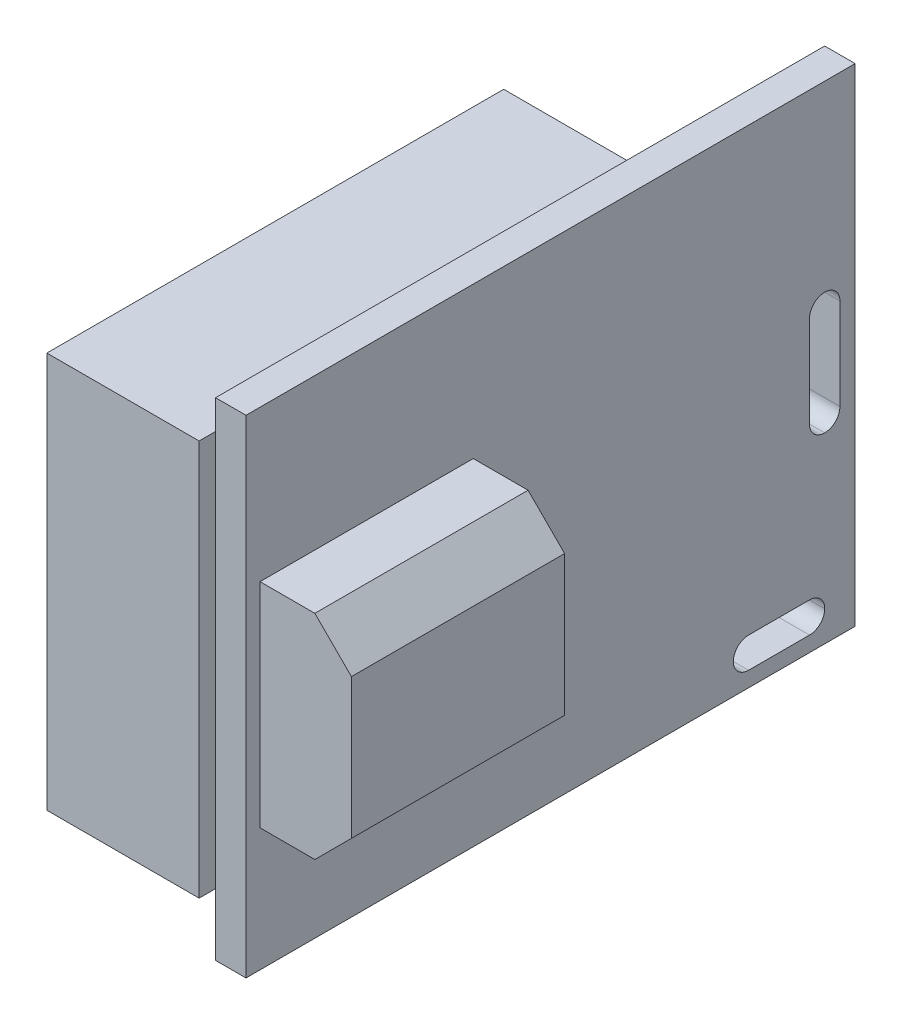
SolidWorks part; units mm, degrees
ref_plane "Спереди" through (0, 0, 0) normal (0, 0, 1) x (1, 0, 0)
ref_plane "Сверху" through (0, 0, 0) normal (0, 1, 0) x (1, 0, 0)
ref_plane "Справа" through (0, 0, 0) normal (1, 0, 0) x (0, 0, -1)
sketch "Эскиз1" plane through (0, 0, 0) normal (0, 0, 1) x (1, 0, 0)
  line L0 (0, 0) -> (3.5391, 0) construction
  line L5 (4.0391, -8) -> (3.0391, -8)
  line L6 (4.0391, -8) -> (4.0391, 8)
  line L7 (4.0391, 8) -> (3.0391, 8)
  line L8 (3.0391, -8) -> (3.0391, 8)
  line L9 (4.0391, -8) -> (3.0391, 8) construction
  line L10 (4.0391, 8) -> (3.0391, -8) construction
  line L11 (7.5, -3.5) -> (4.5, -3.5)
  line L12 (7.5, -3.5) -> (7.5, 3.5)
  line L13 (7.5, 3.5) -> (4.5, 3.5)
  line L14 (4.5, -3.5) -> (4.5, 3.5)
  line L15 (7.5, -3.5) -> (4.5, 3.5) construction
  line L16 (7.5, 3.5) -> (4.5, -3.5) construction
  line L17 (-2.5, -6.5) -> (2.5, -6.5)
  line L18 (-2.5, -6.5) -> (-2.5, 6.5)
  line L19 (-2.5, 6.5) -> (2.5, 6.5)
  line L20 (2.5, -6.5) -> (2.5, 6.5)
  line L21 (-2.5, -6.5) -> (2.5, 6.5) construction
  line L22 (-2.5, 6.5) -> (2.5, -6.5) construction
  line L23 (3.5391, 0) -> (6, 0) construction
  point P0 (0, 0)
  point P5 (3.5391, 0)
  point P10 (6, 0)
  dimension "D1" = 5
  dimension "D2" = 13
  dimension "D3" = 1
  dimension "D4" = 3
  dimension "D5" = 7
  dimension "D6" = 10
  dimension "D7" = 16
extrude "Бобышка-Вытянуть1" add sketch "Эскиз1" against normal blind 20 contours L8 L5 L6 L7 region at (3.5391, 0, 0)
extrude "Бобышка-Вытянуть2" add sketch "Эскиз1<3>" against normal blind 15 separate body contours L17 L20 L19 L18
sketch "Эскиз1<3>" plane through (0, 0, 0) normal (0, 0, 1) x (1, 0, 0) same geometry as "Эскиз1"
extrude "Бобышка-Вытянуть3" add sketch "Эскиз1<4>" against normal blind 7 separate body contours L12 L13 L14 L11
sketch "Эскиз1<4>" plane through (0, 0, 0) normal (0, 0, 1) x (1, 0, 0) same geometry as "Эскиз1"
sketch "Эскиз2" plane through (4.0391, 0, 0) normal (1, 0, 0) x (0, 0, -1)
  line L0 (20, 0) -> (19, 0) construction
  line L1 (20, -8) -> (20, 8) construction
  line L2 (20, -8) -> (0, -8) construction
  line L3 (19.5, -2) -> (18.5, -2)
  line L4 (19.5, -2) -> (19.5, 2)
  line L5 (19.5, 2) -> (18.5, 2)
  line L6 (18.5, -2) -> (18.5, 2)
  line L7 (19.5, -2) -> (18.5, 2) construction
  line L8 (19.5, 2) -> (18.5, -2) construction
  line L9 (16, -7.5) -> (19, -7.5)
  line L10 (16, -7.5) -> (16, -6.5)
  line L11 (16, -6.5) -> (19, -6.5)
  line L12 (19, -7.5) -> (19, -6.5)
  line L13 (16, -7.5) -> (19, -6.5) construction
  line L14 (16, -6.5) -> (19, -7.5) construction
  point P9 (17.5, -7)
  dimension "D1" = 4
  dimension "D2" = 1
  dimension "D3" = 0.5
  dimension "D4" = 3
  dimension "D5" = 1
  dimension "D6" = 0.5
extrude "Вырез-Вытянуть1" cut sketch "Эскиз2" against normal through all
fillet "Скругление1" radius 0.5 8 edges at (3.5391, -2, -18.5) (3.5391, 2, -18.5) (3.5391, 2, -19.5) (3.5391, -2, -19.5) (3.5391, -7.5, -19) (3.5391, -6.5, -19) (3.5391, -6.5, -16) (3.5391, -7.5, -16)
chamfer "Фаска1" distance 1.2 angle 45 2 edges at (7.5, -3.5, -3.5) (7.5, 3.5, -3.5)
